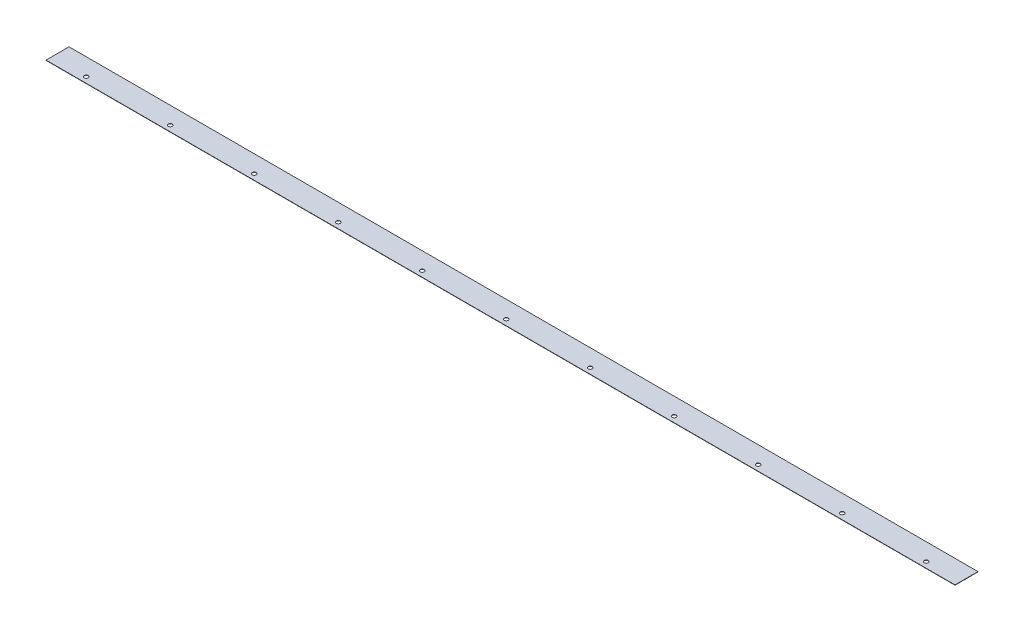
SolidWorks part; units mm, degrees
note: The reader was unsure of these and kept them because the rebuilt part matched: thickness of "Base-Flange1", "Sheet-Metal1", "Sheet-Metal2", "Sheet-Metal3".
material "AISI 304"
ref_plane "Front Plane" through (0, 0, 0) normal (0, 0, 1) x (1, 0, 0)
ref_plane "Top Plane" through (0, 0, 0) normal (0, 1, 0) x (1, 0, 0)
ref_plane "Right Plane" through (0, 0, 0) normal (1, 0, 0) x (0, 0, -1)
sketch "Sketch1" plane through (0, 0, 0) normal (0, 1, 0) x (1, 0, 0)
  line L1 (-790, -20) -> (790, -20)
  line L2 (-790, -20) -> (-790, 20)
  line L3 (-790, 20) -> (790, 20)
  line L4 (790, -20) -> (790, 20)
  line L5 (-790, -20) -> (790, 20) construction
  line L6 (-790, 20) -> (790, -20) construction
  point P0 (0, 0)
  dimension "D1" = 40
  dimension "D2" = 1580
base flange "Base-Flange1" sketch "Sketch1" thickness 0.5 reverse thickness direction no parameters "D1"=0
sketch "Sketch6" plane through (0, 0, 0) normal (0, 1, 0) x (1, 0, 0)
  line L0 (-790, -20) -> (790, -20) construction
  circle A0 centre (0, -10) radius 3.5
  dimension "D1" = 7
  dimension "D2" = 10
extrude "Cut-Extrude1" cut sketch "Sketch6" against normal blind 10 normal cut yes
pattern_linear "LPattern1" count 6 spacing 146 along (-1, 0, 0) count 6 spacing 146 along (1, 0, 0) of "Cut-Extrude1"
sketch "Bend-Lines1" [suppressed] plane through (0, 0, 0) normal (0, 1, 0) x (1, 0, 0)
sketch "Bounding-Box1" [suppressed] plane through (0, 0, 0) normal (0, 1, 0) x (1, 0, 0)
sheet metal parameters "Sheet-Metal1" thickness 0.5 parameters "D1"=0
flat pattern "Flat-Pattern1" [suppressed]
sketch "Bend-Lines2" plane through (0, 0, 0) normal (0, 1, 0) x (1, 0, 0)
sketch3d "Bounding-Box2" [suppressed]
  line L0 (-790, 10, 0) -> (790, 10, 0) construction
  line L1 (-790, -10, 0) -> (790, -10, 0) construction
  line L2 (-790, 10, 0) -> (-790, -10, 0) construction
  line L3 (790, 10, 0) -> (790, -10, 0) construction
sheet metal parameters "Sheet-Metal2" thickness 0.5 parameters "D1"=0, "D7"=2
flat pattern "Flat-Pattern1"
sketch "Bend-Lines2" plane through (0, 0, 0) normal (0, 1, 0) x (1, 0, 0)
sketch3d "Bounding-Box2" [suppressed]
  line L0 (790, 10, 0) -> (-790, 10, 0) construction
  line L1 (790, -10, 0) -> (-790, -10, 0) construction
  line L2 (790, 10, 0) -> (790, -10, 0) construction
  line L3 (-790, 10, 0) -> (-790, -10, 0) construction
sheet metal parameters "Sheet-Metal3" thickness 0.5 parameters "D1"=0, "D7"=2
flat pattern "Flat-Pattern1"
sketch "Bend-Lines2" plane through (0, 0, 0) normal (0, 1, 0) x (1, 0, 0)
sketch3d "Bounding-Box2" [suppressed]
  line L0 (790, 20, 0) -> (-790, 20, 0) construction
  line L1 (790, -20, 0) -> (-790, -20, 0) construction
  line L2 (790, 20, 0) -> (790, -20, 0) construction
  line L3 (-790, 20, 0) -> (-790, -20, 0) construction
